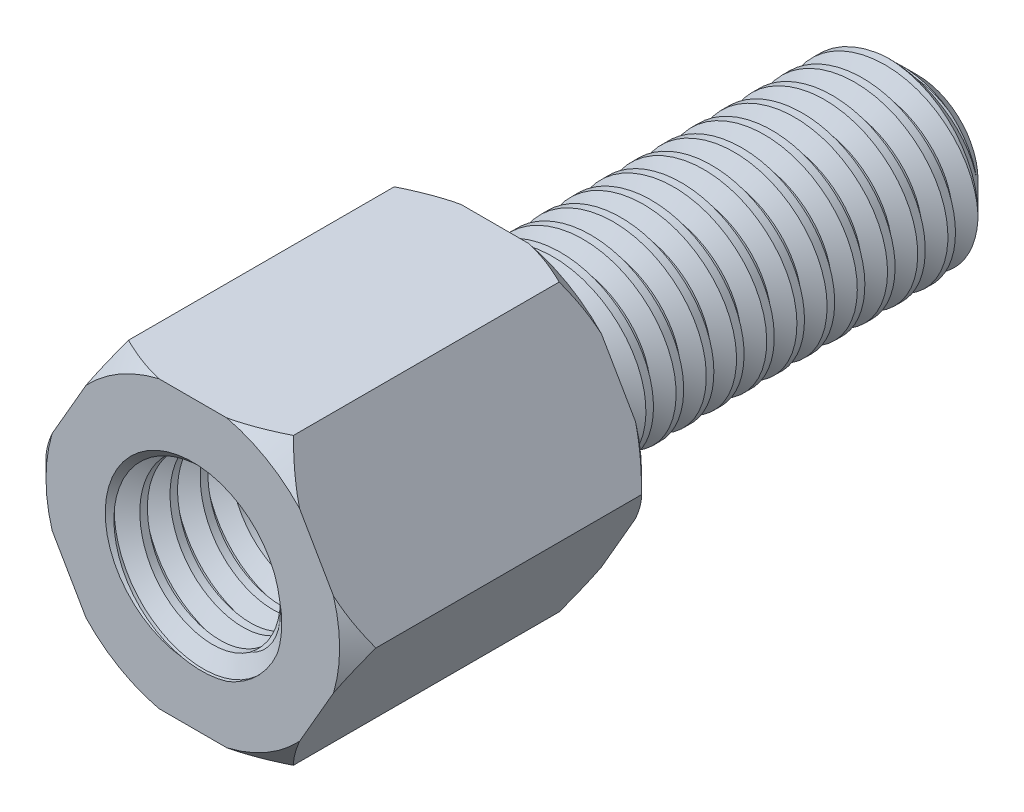
SolidWorks part; units mm, degrees
ref_plane "Front Plane" through (0, 0, 0) normal (0, 0, 1) x (1, 0, 0)
ref_plane "Top Plane" through (0, 0, 0) normal (0, 1, 0) x (1, 0, 0)
ref_plane "Right Plane" through (0, 0, 0) normal (1, 0, 0) x (0, 0, -1)
sketch "Sketch1" plane through (0, 0, 0) normal (0, 0, 1) x (1, 0, 0)
  line L1 (-2.7309, 0) -> (-1.3654, -2.365)
  line L2 (-1.3654, -2.365) -> (1.3654, -2.365)
  line L3 (1.3654, -2.365) -> (2.7309, 0)
  line L4 (2.7309, 0) -> (1.3654, 2.365)
  line L5 (1.3654, 2.365) -> (-1.3654, 2.365)
  line L6 (-1.3654, 2.365) -> (-2.7309, 0)
  circle A0 centre (0, 0) radius 2.365 construction
  dimension "D1" = 4.73
extrude "Boss-Extrude1" add sketch "Sketch1" along normal blind 5
sketch "Sketch3" plane through (0, 0, 0) normal (0, 1, 0) x (1, 0, 0)
  line L0 (-1.2, 0) -> (-1.2, 0.6)
  line L1 (1.3654, 0) -> (-1.3654, 0) construction
  line L2 (-1.2, 0.6) -> (-1.5, 0.6)
  line L3 (-1.5, 0.6) -> (-1.5, 7)
  line L4 (-1.5, 7) -> (0, 7)
  line L5 (0, 7) -> (0, 0)
  line L6 (0, 0) -> (-1.2, 0)
  dimension "D1" = 1.5
  dimension "D2" = 1.2
  dimension "D3" = 7
  dimension "D4" = 0.6
revolve "Revolve1" add sketch "Sketch3" angle 360 about L5
chamfer "Chamfer2" distance 0.5 angle 45 1 edges at (-1.5, 0, -7)
thread "Thread1" pitch 0.5 method cut profile "Thread Profile1" start angle 0, offset 0.5, length 7, pitch 0.5, diameter 3
ref_plane "Plane1" through (1.5, 0, -7.5) normal (0, 1, 0) x (-1, 0, 0)
sketch "Thread Profile1" plane through (1.5, 0, -7.5) normal (0, 1, 0) x (-1, 0, 0)
  line L0 (0, 0) -> (0, 0.5) construction
  line L1 (0, 0) -> (0.2706, 0.1562)
  line L2 (0.2706, 0.1562) -> (0.2706, 0.2187)
  line L3 (0.2706, 0.2187) -> (0, 0.375)
  line L4 (0.2706, 0.1875) -> (0, 0.1875) construction
  line L11 (0, 0) -> (0, 0.375)
  point P2 (0, 0)
  dimension "Pitch" = 0.5
  dimension "Profile_Angle" = 60
  dimension "Profile_Land" = 0.0625
  dimension "Profile_Height" = 0.2706
hole_wizard "Tap Drill for M3 Tap1" positions "Sketch9" profile "Sketch10" hole size "M3" standard "DIN"
sketch "Sketch9" plane through (0, 0, 5) normal (0, 0, 1) x (1, 0, 0)
  point P0 (0, 0)
sketch "Sketch10" plane through (0, 0, 5) normal (1, 0, 0) x (0, -1, 0)
  line L0 (0, 0) -> (0, 4.7511)
  line L1 (0, 4.7511) -> (1.25, 4)
  line L2 (1.25, 4) -> (1.25, 0)
  line L5 (1.25, 0) -> (0, 0)
  line L10 (0, 4.7511) -> (-1.25, 4) construction
  line L11 (0, -6.35) -> (0, 107.95) construction
  dimension "Hole Dia." = 2.5
  dimension "Hole Depth" = 4
  dimension "Drill Angle" = 118
chamfer "Chamfer3" distance 0.2 angle 45 1 edges at (1.25, 0, 5)
thread "Thread2" pitch 0.5 method cut trim with start face yes trim with end face yes profile "Thread Profile2" start angle 0, offset 0.5, length 4, pitch 0.5, diameter 2.5
ref_plane "Plane2" through (-1.25, 0, 5.5) normal (0, -1, 0) x (-1, 0, 0)
sketch "Thread Profile2" plane through (-1.25, 0, 5.5) normal (0, -1, 0) x (-1, 0, 0)
  line L0 (0, 0) -> (0, 0.5) construction
  line L1 (0, 0) -> (0.2706, 0.1562)
  line L2 (0.2706, 0.1562) -> (0.2706, 0.2187)
  line L3 (0.2706, 0.2187) -> (0, 0.375)
  line L4 (0.2706, 0.1875) -> (0, 0.1875) construction
  line L11 (0, 0) -> (0, 0.375)
  point P2 (0, 0)
  dimension "Pitch" = 0.5
  dimension "Profile_Angle" = 60
  dimension "Profile_Land" = 0.0625
  dimension "Profile_Height" = 0.2706
sketch "Sketch13" plane through (0, 0, 0) normal (0, 1, 0) x (1, 0, 0)
  line L0 (-2.7309, -5) -> (-2.7309, -4.7)
  line L1 (-2.7309, -5) -> (-2.7309, 0) construction
  line L2 (-2.7309, -4.7) -> (-2.4309, -5)
  line L3 (-1.3654, -5) -> (-2.7309, -5) construction
  line L4 (-2.4309, -5) -> (-2.7309, -5)
  line L5 (-2.7309, 0) -> (-2.7309, -0.3)
  line L6 (-2.7309, -0.3) -> (-2.4309, 0)
  line L7 (-1.3654, 0) -> (-2.7309, 0) construction
  line L8 (-2.4309, 0) -> (-2.7309, 0)
  line L9 (0, 0) -> (0, -5) construction
  line L10 (1.3654, 0) -> (-1.3654, 0) construction
  line L11 (1.3654, -5) -> (-1.3654, -5) construction
  dimension "D1" = 0.3
  dimension "D2" = 0.3
  dimension "D3" = 0.3
  dimension "D4" = 0.3
revolve "Cut-Revolve10" cut sketch "Sketch13" angle 360 about L9
